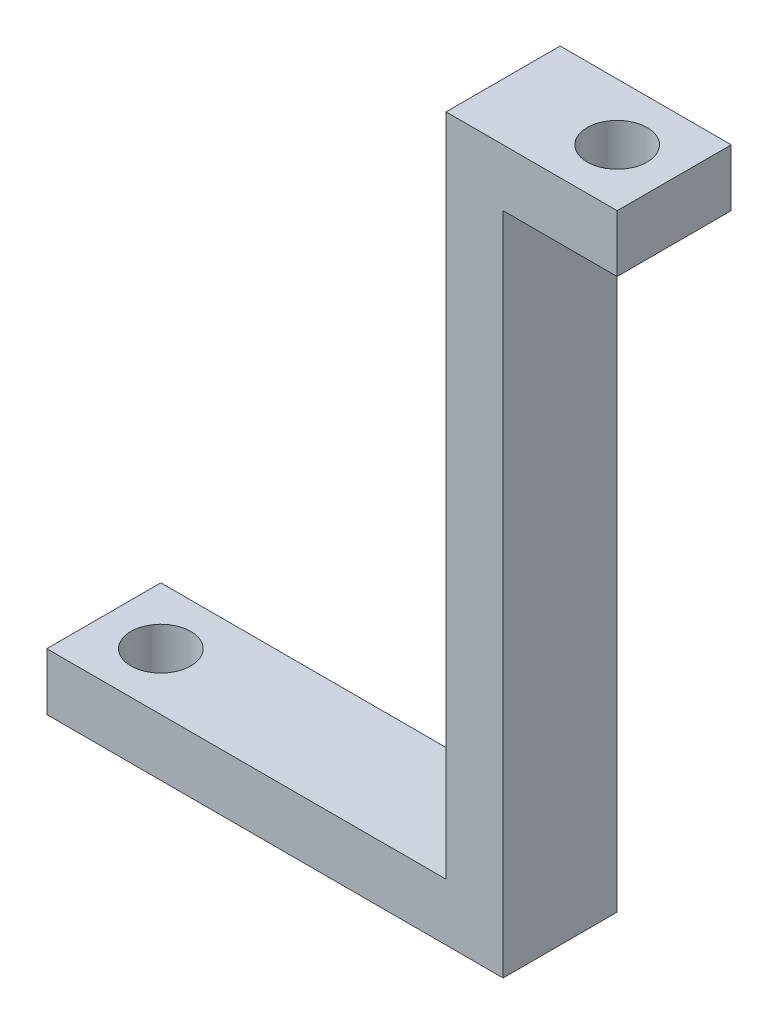
SolidWorks part; units mm, degrees
ref_plane "Front Plane" through (0, 0, 0) normal (0, 0, 1) x (1, 0, 0)
ref_plane "Top Plane" through (0, 0, 0) normal (0, 1, 0) x (1, 0, 0)
ref_plane "Right Plane" through (0, 0, 0) normal (1, 0, 0) x (0, 0, -1)
sketch "Sketch1" plane through (0, 0, 0) normal (0, 1, 0) x (1, 0, 0)
  line L0 (0, 0) -> (-2, 0) construction
  line L1 (-2, 2) -> (12, 2)
  line L2 (-2, 2) -> (-2, -2)
  line L3 (-2, -2) -> (12, -2)
  line L4 (12, 2) -> (12, -2)
  line L5 (0, 0) -> (0, -2) construction
  circle A0 centre (0, 0) radius 1.05
  point P0 (0, 0)
  dimension "D3" = 2.1
  dimension "D1" = 12
  dimension "D2" = 4
  dimension "D4" = 2
extrude "Boss-Extrude1" add sketch "Sketch1" along normal blind 2
sketch "Sketch2" plane through (0, 0, 0) normal (0, 1, 0) x (1, 0, 0)
  line L0 (12, -2) -> (14, -2)
  line L2 (14, -2) -> (14, 2)
  line L3 (14, 2) -> (12, 2)
  line L4 (12, -2) -> (12, 2) construction
  line L5 (12, 2) -> (12, -2)
  dimension "D1" = 2
extrude "Boss-Extrude2" add sketch "Sketch2" along normal up to surface (25.3 mm away) up to face at (5, 0, 0)
sketch "Sketch3" plane through (0, 25.3, 0) normal (0, 1, 0) x (1, 0, 0)
  line L8 (14, 2) -> (18, 2)
  line L9 (18, 2) -> (18, -2)
  line L10 (18, -2) -> (14, -2)
  line L11 (14, 2) -> (14, -2)
  line L13 (16, 0) -> (18, 0) construction
  line L14 (16, 0) -> (16, 2) construction
  circle A2 centre (16, 0) radius 1.05
  dimension "D2" = 2.1
  dimension "D1" = 4
extrude "Boss-Extrude3" add sketch "Sketch3" against normal blind 2
